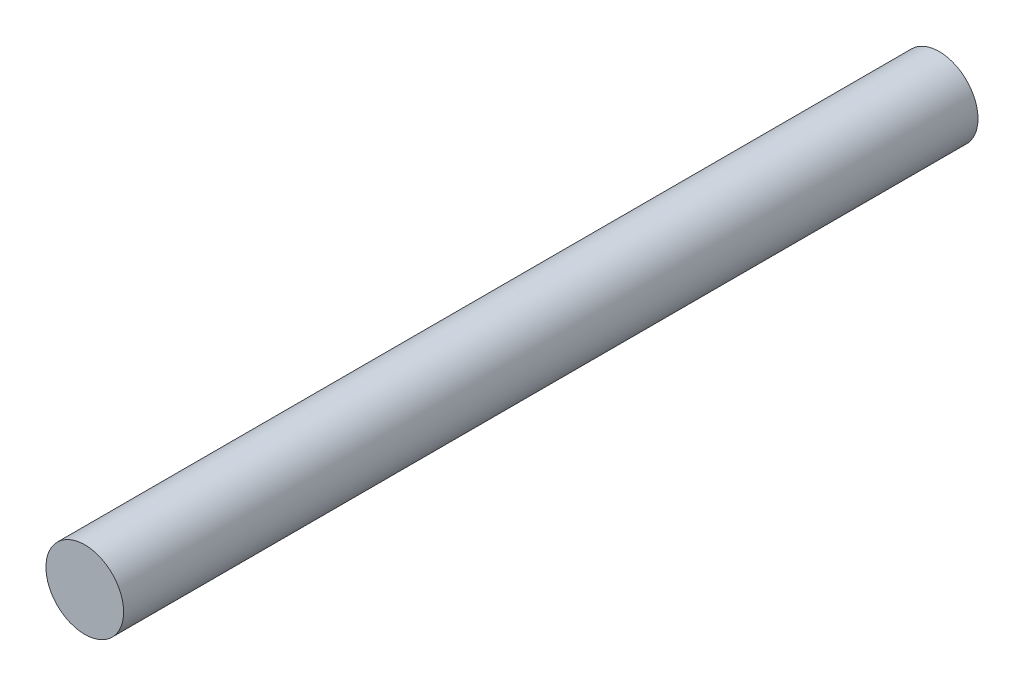
SolidWorks part; units mm, degrees
material "Hexcel AS4C (3000 Filaments)"
ref_plane "Front" through (0, 0, 0) normal (0, 0, 1) x (1, 0, 0)
ref_plane "Top" through (0, 0, 0) normal (0, 1, 0) x (1, 0, 0)
ref_plane "Right" through (0, 0, 0) normal (1, 0, 0) x (0, 0, -1)
sketch "Sketch1" plane through (0, 0, 0) normal (0, 0, 1) x (1, 0, 0)
  circle A0 centre (0, 0) radius 3.175
  dimension "D1" = 6.35
extrude "Boss-Extrude1" add sketch "Sketch1" along normal blind 69.85
equation "\"truss_member_od\" = .25in"
equation "\"truss_member_id\" = 0in"
equation "\"truss_member_L1\" = 2.75in"
equation "\"D1@Sketch1\"=\"truss_member_od\""
equation "\"D1@Boss-Extrude1\"=\"truss_member_L2\""
equation "\"truss_member_L2\" = 2.75in"
equation "\"connector_hole_depth\" = .375in"
